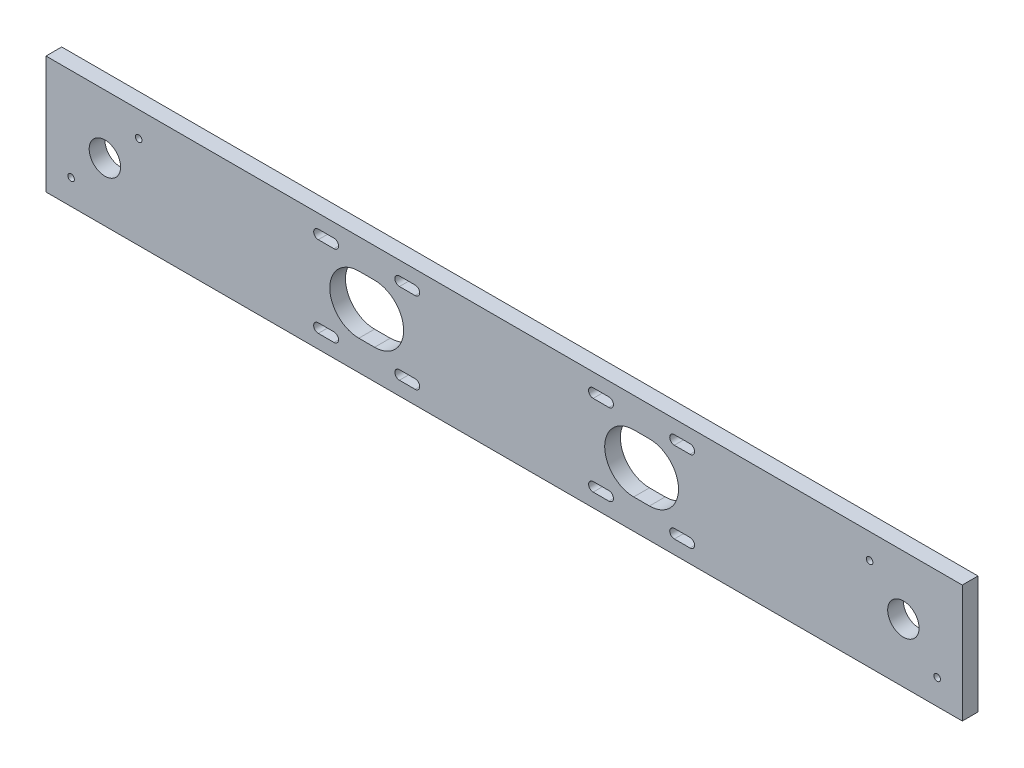
SolidWorks part; units mm, degrees
ref_plane "Alzado" through (0, 0, 0) normal (0, 0, 1) x (1, 0, 0)
ref_plane "Planta" through (0, 0, 0) normal (0, 1, 0) x (1, 0, 0)
ref_plane "Vista lateral" through (0, 0, 0) normal (1, 0, 0) x (0, 0, -1)
sketch "Croquis1" plane through (0, 0, 0) normal (0, 0, 1) x (1, 0, 0)
  line L1 (-350, -45) -> (0, -45)
  line L2 (-350, -45) -> (-350, 0)
  line L3 (-350, 0) -> (0, 0)
  line L4 (0, -45) -> (0, 0)
  dimension "D1" = 350
  dimension "D2" = 45
extrude "Saliente-Extruir1" add sketch "Croquis1" along normal blind 6 contours L3 L4 L1 L2
sketch "Croquis2" plane through (0, 0, 6) normal (0, 0, 1) x (1, 0, 0)
  line L0 (-350, -45) -> (-350, 0) construction
  line L1 (0, -45) -> (0, 0) construction
  line L2 (-350, -45) -> (0, -45) construction
  line L3 (-340.4047, -35.4047) -> (-314.5953, -9.5953) construction
  line L4 (-35.4047, -9.5953) -> (-9.5953, -35.4047) construction
  line L5 (-350, 0) -> (0, 0) construction
  circle A0 centre (-327.5, -22.5) radius 6
  circle A1 centre (-22.5, -22.5) radius 6
  circle A2 centre (-327.5, -22.5) radius 18.25 construction
  circle A4 centre (-314.5953, -9.5953) radius 1.25
  circle A5 centre (-340.4047, -35.4047) radius 1.25
  circle A6 centre (-22.5, -22.5) radius 18.25 construction
  circle A7 centre (-35.4047, -9.5953) radius 1.25
  circle A8 centre (-9.5953, -35.4047) radius 1.25
  circle A9 centre (-22.5, -22.5) radius 21 construction
  circle A10 centre (-327.5, -22.5) radius 21 construction
  dimension "D1" = 12
  dimension "D2" = 12
  dimension "D7" = 36.5
  dimension "D9" = 2.5
  dimension "D10" = 2.5
  dimension "D11" = 36.5
  dimension "D13" = 2.5
  dimension "D14" = 2.5
  dimension "D15" = 42
  dimension "D16" = 42
  dimension "D3" = 22.5
  dimension "D4" = 22.5
  dimension "D5" = 22.5
  dimension "D6" = 22.5
  dimension "D8" = 45
  dimension "D12" = 45
extrude "Cortar-Extruir1" cut sketch "Croquis2" against normal through all
sketch "Croquis3" plane through (0, 0, 6) normal (0, 0, 1) x (1, 0, 0)
  line L2 (-246, -7) -> (-240, -7) construction
  line L3 (-141, -7) -> (-135, -7) construction
  line L4 (-141, -5.25) -> (-135, -5.25)
  line L5 (-141, -8.75) -> (-135, -8.75)
  line L6 (-125.5, -22.5) -> (-119.5, -22.5) construction
  line L7 (-125.5, -11.4) -> (-119.5, -11.4)
  line L8 (-125.5, -33.6) -> (-119.5, -33.6)
  line L9 (-350, 0) -> (0, 0) construction
  line L10 (-141, -38) -> (-135, -38) construction
  line L11 (-141, -36.25) -> (-135, -36.25)
  line L12 (-141, -39.75) -> (-135, -39.75)
  line L13 (-110, -7) -> (-104, -7) construction
  line L14 (-110, -5.25) -> (-104, -5.25)
  line L15 (-110, -8.75) -> (-104, -8.75)
  line L16 (-110, -38) -> (-104, -38) construction
  line L17 (-110, -36.25) -> (-104, -36.25)
  line L18 (-110, -39.75) -> (-104, -39.75)
  line L19 (-246, -5.25) -> (-240, -5.25)
  line L20 (-246, -8.75) -> (-240, -8.75)
  line L21 (-230.5, -22.5) -> (-224.5, -22.5) construction
  line L22 (-230.5, -11.4) -> (-224.5, -11.4)
  line L23 (-230.5, -33.6) -> (-224.5, -33.6)
  line L24 (-246, -38) -> (-240, -38) construction
  line L25 (-246, -36.25) -> (-240, -36.25)
  line L26 (-246, -39.75) -> (-240, -39.75)
  line L27 (-215, -7) -> (-209, -7) construction
  line L28 (-215, -5.25) -> (-209, -5.25)
  line L29 (-215, -8.75) -> (-209, -8.75)
  line L30 (-215, -38) -> (-209, -38) construction
  line L31 (-215, -36.25) -> (-209, -36.25)
  line L32 (-215, -39.75) -> (-209, -39.75)
  line L33 (-350, 0) -> (0, 0) construction
  arc A2 (-246, -5.25) -> (-246, -8.75) centre (-246, -7) ccw
  arc A5 (-141, -5.25) -> (-141, -8.75) centre (-141, -7) ccw
  arc A6 (-135, -8.75) -> (-135, -5.25) centre (-135, -7) ccw
  arc A7 (-125.5, -11.4) -> (-125.5, -33.6) centre (-125.5, -22.5) ccw
  arc A8 (-119.5, -33.6) -> (-119.5, -11.4) centre (-119.5, -22.5) ccw
  circle A9 centre (-22.5, -22.5) radius 6 construction
  arc A11 (-141, -36.25) -> (-141, -39.75) centre (-141, -38) ccw
  arc A12 (-135, -39.75) -> (-135, -36.25) centre (-135, -38) ccw
  arc A13 (-110, -5.25) -> (-110, -8.75) centre (-110, -7) ccw
  arc A14 (-104, -8.75) -> (-104, -5.25) centre (-104, -7) ccw
  arc A15 (-110, -36.25) -> (-110, -39.75) centre (-110, -38) ccw
  arc A16 (-104, -39.75) -> (-104, -36.25) centre (-104, -38) ccw
  arc A17 (-240, -8.75) -> (-240, -5.25) centre (-240, -7) ccw
  arc A18 (-230.5, -11.4) -> (-230.5, -33.6) centre (-230.5, -22.5) ccw
  arc A19 (-224.5, -33.6) -> (-224.5, -11.4) centre (-224.5, -22.5) ccw
  arc A20 (-246, -36.25) -> (-246, -39.75) centre (-246, -38) ccw
  arc A21 (-240, -39.75) -> (-240, -36.25) centre (-240, -38) ccw
  arc A22 (-215, -5.25) -> (-215, -8.75) centre (-215, -7) ccw
  arc A23 (-209, -8.75) -> (-209, -5.25) centre (-209, -7) ccw
  arc A24 (-215, -36.25) -> (-215, -39.75) centre (-215, -38) ccw
  arc A25 (-209, -39.75) -> (-209, -36.25) centre (-209, -38) ccw
  circle A26 centre (-327.5, -22.5) radius 6 construction
  point P2 (-122.5, -22.5)
  point P12 (-138, -7)
  point P20 (-227.5, -22.5)
  point P23 (-138, -38)
  point P30 (-107, -7)
  point P37 (-107, -38)
  point P48 (-243, -7)
  point P55 (-243, -38)
  point P62 (-212, -7)
  point P69 (-212, -38)
  point P74 (-254.3336, -20.2482)
  dimension "D5" = 1.75
  dimension "D4" = 22.2
  dimension "D9" = 15.5
  dimension "D18" = 1.75
  dimension "D19" = 1.75
  dimension "D20" = 1.75
  dimension "D21" = 1.75
  dimension "D36" = 1.75
  dimension "D37" = 1.75
  dimension "D38" = 1.75
  dimension "D1" = 100
  dimension "D2" = 22.5
  dimension "D3" = 6
  dimension "D6" = 15.5
  dimension "D7" = 6
  dimension "D8" = 15.5
  dimension "D10" = 15.5
  dimension "D11" = 15.5
  dimension "D12" = 15.5
  dimension "D13" = 6
  dimension "D14" = 6
  dimension "D15" = 6
  dimension "D16" = 15.5
  dimension "D17" = 15.5
  dimension "D22" = 6
  dimension "D23" = 6
  dimension "D24" = 22.2
  dimension "D25" = 15.5
  dimension "D26" = 15.5
  dimension "D27" = 15.5
  dimension "D28" = 15.5
  dimension "D29" = 15.5
  dimension "D30" = 15.5
  dimension "D31" = 6
  dimension "D32" = 6
  dimension "D33" = 6
  dimension "D34" = 15.5
  dimension "D35" = 15.5
  dimension "D39" = 100
  dimension "D40" = 22.5
extrude "Cortar-Extruir2" cut sketch "Croquis3" against normal through all
